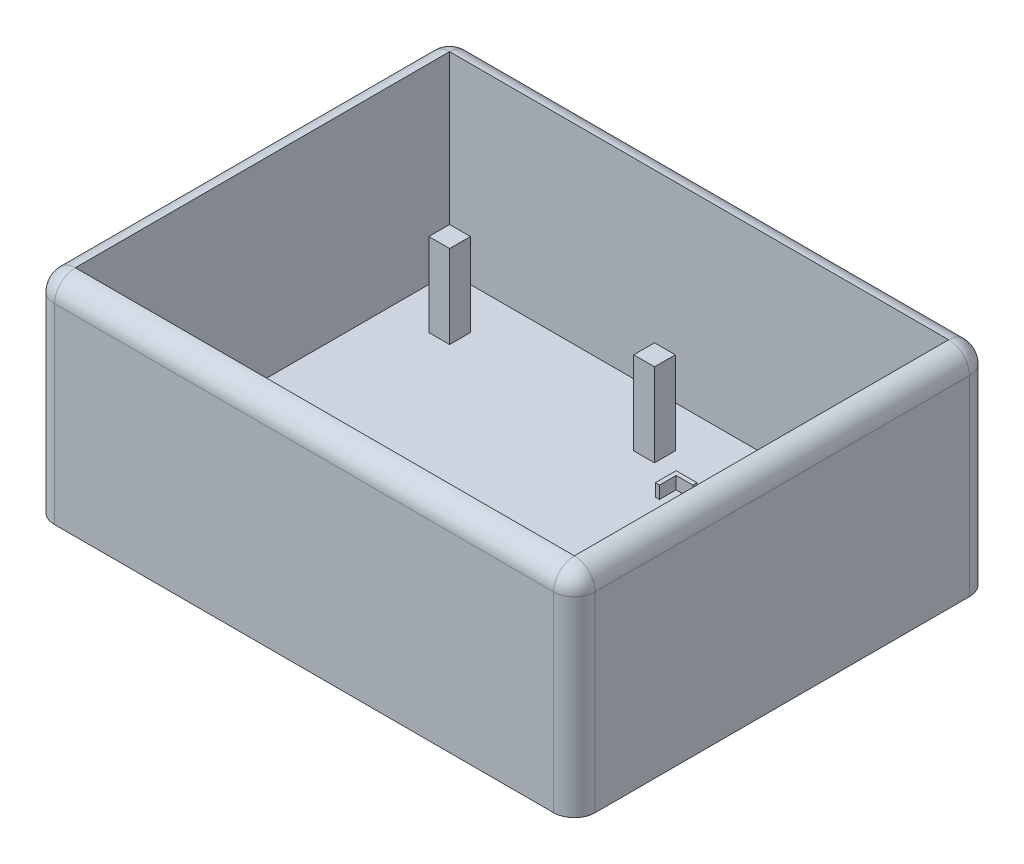
SolidWorks part; units mm, degrees
ref_plane "Front Plane" through (0, 0, 0) normal (0, 0, 1) x (1, 0, 0)
ref_plane "Top Plane" through (0, 0, 0) normal (0, 1, 0) x (1, 0, 0)
ref_plane "Right Plane" through (0, 0, 0) normal (1, 0, 0) x (0, 0, -1)
sketch "Sketch1" plane through (0, 0, 0) normal (0, 1, 0) x (1, 0, 0)
  line L1 (-65, 50) -> (65, 50)
  line L2 (-65, 50) -> (-65, -50)
  line L3 (-65, -50) -> (65, -50)
  line L4 (65, 50) -> (65, -50)
  line L5 (-65, 50) -> (65, -50) construction
  line L6 (-65, -50) -> (65, 50) construction
  point P0 (0, 0)
  dimension "D1" = 130
  dimension "D2" = 100
extrude "Boss-Extrude1" add sketch "Sketch1" along normal blind 51
sketch "Sketch2" plane through (0, 51, 0) normal (0, 1, 0) x (1, 0, 0)
  line L0 (-65, 50) -> (-65, -50) construction
  line L1 (-60, -45) -> (60, -45)
  line L2 (-60, -45) -> (-60, 45)
  line L3 (-60, 45) -> (60, 45)
  line L4 (60, -45) -> (60, 45)
  line L5 (-60, -45) -> (60, 45) construction
  line L6 (-60, 45) -> (60, -45) construction
  line L7 (65, 50) -> (-65, 50) construction
  point P0 (0, 0)
  dimension "D1" = 5
  dimension "D2" = 5
extrude "Cut-Extrude1" cut sketch "Sketch2" against normal blind 46
fillet "Fillet2" radius 5 4 edges at (0, 51, -50) (65, 51, 0) (0, 51, 50) (-65, 51, 0)
fillet "Fillet4" radius 5 8 edges at (65, 23, -50) (-65, 23, -50) (65, 23, 50) (-65, 23, 50) (63.5355, 49.5355, -48.5355) (-63.5355, 49.5355, -48.5355) (63.5355, 49.5355, 48.5355) (-63.5355, 49.5355, 48.5355)
sketch "Sketch6" plane through (0, 5, 0) normal (0, 1, 0) x (1, 0, 0)
  line L0 (60, 45) -> (-60, 45) construction
  line L1 (-50, 35) -> (-45, 35)
  line L2 (-50, 35) -> (-50, 30)
  line L3 (-50, 30) -> (-45, 30)
  line L4 (-45, 35) -> (-45, 30)
  line L5 (-50, 35) -> (-45, 30) construction
  line L6 (-50, 30) -> (-45, 35) construction
  line L7 (-50, -29.03) -> (-45, -29.03)
  line L8 (-50, -29.03) -> (-50, -34.03)
  line L9 (-50, -34.03) -> (-45, -34.03)
  line L10 (-45, -29.03) -> (-45, -34.03)
  line L11 (-50, -29.03) -> (-45, -34.03) construction
  line L12 (-50, -34.03) -> (-45, -29.03) construction
  line L13 (-0.73, 35) -> (4.27, 35)
  line L14 (-0.73, 35) -> (-0.73, 30)
  line L15 (-0.73, 30) -> (4.27, 30)
  line L16 (4.27, 35) -> (4.27, 30)
  line L17 (-0.73, 35) -> (4.27, 30) construction
  line L18 (-0.73, 30) -> (4.27, 35) construction
  line L24 (-0.73, -29.03) -> (4.27, -29.03)
  line L25 (-60, 45) -> (-60, -45) construction
  line L26 (-0.73, -29.03) -> (-0.73, -34.03)
  line L27 (-0.73, -34.03) -> (4.27, -34.03)
  line L28 (4.27, -29.03) -> (4.27, -34.03)
  line L29 (-0.73, -29.03) -> (4.27, -34.03) construction
  line L30 (-0.73, -34.03) -> (4.27, -29.03) construction
  point P0 (-47.5, 32.5)
  point P5 (-47.5, -31.53)
  point P10 (1.77, 32.5)
  point P15 (1.77, -31.53)
  dimension "D1" = 5
  dimension "D2" = 5
  dimension "D3" = 5
  dimension "D4" = 5
  dimension "D5" = 44.27
  dimension "D6" = 59.03
  dimension "D7" = 10
  dimension "D8" = 10
extrude "Boss-Extrude2" add sketch "Sketch6" along normal blind 20
sketch "Sketch9" plane through (0, 5, 0) normal (0, 1, 0) x (1, 0, 0)
  line L0 (11.5, -14.03) -> (11.5, -19.03)
  line L1 (11.5, -19.03) -> (16.5, -19.03)
  line L2 (16.5, -19.03) -> (16.5, -18.03)
  line L3 (16.5, -18.03) -> (12.5, -18.03)
  line L4 (12.5, -18.03) -> (12.5, -14.03)
  line L5 (12.5, -14.03) -> (11.5, -14.03)
  line L6 (11.5, 27.97) -> (16.5, 27.97)
  line L7 (16.5, 27.97) -> (16.5, 26.97)
  line L8 (16.5, 26.97) -> (12.5, 26.97)
  line L9 (12.5, 26.97) -> (12.5, 22.97)
  line L10 (12.5, 22.97) -> (11.5, 22.97)
  line L11 (11.5, 22.97) -> (11.5, 27.97)
  line L12 (40, 27.97) -> (40, 22.97)
  line L13 (40, 22.97) -> (39, 22.97)
  line L14 (39, 22.97) -> (39, 26.97)
  line L15 (39, 26.97) -> (35, 26.97)
  line L16 (35, 26.97) -> (35, 27.97)
  line L17 (35, 27.97) -> (40, 27.97)
  line L18 (40, -19.03) -> (35, -19.03)
  line L19 (35, -19.03) -> (35, -18.03)
  line L20 (35, -18.03) -> (39, -18.03)
  line L21 (39, -18.03) -> (39, -14.03)
  line L22 (39, -14.03) -> (40, -14.03)
  line L23 (40, -14.03) -> (40, -19.03)
  line L24 (60, -45) -> (60, 45) construction
  line L25 (4.27, -29.03) -> (-0.73, -29.03) construction
  dimension "D1" = 5
  dimension "D2" = 1
  dimension "D3" = 5
  dimension "D4" = 1
  dimension "D5" = 1
  dimension "D6" = 5
  dimension "D7" = 1
  dimension "D8" = 5
  dimension "D9" = 1
  dimension "D10" = 5
  dimension "D11" = 5
  dimension "D12" = 1
  dimension "D13" = 5
  dimension "D14" = 5
  dimension "D15" = 1
  dimension "D16" = 1
  dimension "D17" = 45
  dimension "D18" = 26.5
  dimension "D19" = 20
  dimension "D20" = 10
extrude "Boss-Extrude3" add sketch "Sketch9" along normal blind 3
